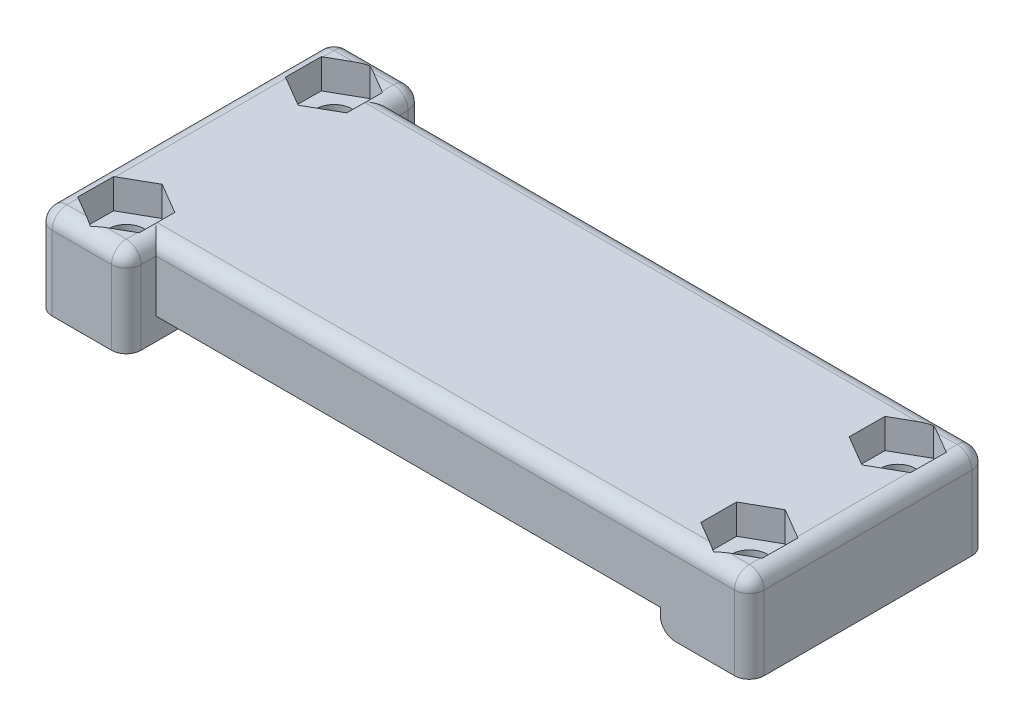
SolidWorks part; units mm, degrees
material "ABS PC"
ref_plane "前基準面" through (0, 0, 0) normal (0, 0, 1) x (1, 0, 0)
ref_plane "上基準面" through (0, 0, 0) normal (0, 1, 0) x (1, 0, 0)
ref_plane "右基準面" through (0, 0, 0) normal (1, 0, 0) x (0, 0, -1)
sketch "草圖1" plane through (0, 0, 0) normal (0, 1, 0) x (1, 0, 0)
  line L0 (0, 0) -> (-20, 0) construction
  line L1 (-20, -8) -> (20, -8)
  line L2 (-20, -4) -> (-20, 4)
  line L3 (-20, 8) -> (20, 8)
  line L4 (20, -8) -> (20, 8)
  line L5 (-20, 4) -> (-26, 4)
  line L6 (-26, 4) -> (-26, 10)
  line L7 (-26, 10) -> (-20, 10)
  line L8 (-20, 10) -> (-20, 8)
  line L9 (-20, -10) -> (-20, -8)
  line L10 (-26, -10) -> (-20, -10)
  line L11 (-26, -4) -> (-26, -10)
  line L12 (-20, -4) -> (-26, -4)
  dimension "D1" = 16
  dimension "D3" = 20
  dimension "D4" = 40
extrude "填料-伸長1" add sketch "草圖1" along normal blind 6
sketch "草圖2" plane through (0, 0, 0) normal (0, 1, 0) x (1, 0, 0)
  line L1 (-26, 4) -> (-20, 4)
  line L2 (-26, 4) -> (-26, -4)
  line L3 (-26, -4) -> (-20, -4)
  line L4 (-20, 4) -> (-20, -4)
extrude "填料-伸長2" add sketch "草圖2" along normal blind 6
sketch "草圖4" plane through (0, 0, 0) normal (0, 1, 0) x (1, 0, 0)
  line L0 (-20, 0) -> (0, 0) construction
  line L1 (-26, 10) -> (-23, 10) construction
  line L2 (-26, -10) -> (-23, -10) construction
  line L3 (-26, 10) -> (-20, 10) construction
  line L4 (-23, 10) -> (-23, 7) construction
  line L5 (-23, -10) -> (-23, -7) construction
  line L6 (-25.0866, -8.1859) -> (-23.0163, -9.4)
  line L7 (-20.9297, -8.2141) -> (-20.9134, -5.8141)
  line L8 (-23.0163, -9.4) -> (-20.9297, -8.2141)
  line L9 (-22.9837, -4.6) -> (-25.0703, -5.7859)
  line L10 (-22.9837, 9.4) -> (-25.0703, 8.2141)
  line L11 (-25.0703, 8.2141) -> (-25.0866, 5.8141)
  line L12 (-25.0866, 5.8141) -> (-23.0163, 4.6)
  line L13 (-23.0163, 4.6) -> (-20.9297, 5.7859)
  line L14 (-20.9297, 5.7859) -> (-20.9134, 8.1859)
  line L15 (-20.9134, 8.1859) -> (-22.9837, 9.4)
  line L16 (-25.0703, -5.7859) -> (-25.0866, -8.1859)
  line L17 (-20.9134, -5.8141) -> (-22.9837, -4.6)
  line L19 (19.0866, 6.1859) -> (17.0163, 7.4)
  line L20 (14.9297, 6.2141) -> (14.9134, 3.8141)
  line L21 (14.9134, 3.8141) -> (16.9837, 2.6)
  line L22 (16.9837, 2.6) -> (19.0703, 3.7859)
  line L23 (17.0163, 7.4) -> (14.9297, 6.2141)
  line L24 (19.0703, 3.7859) -> (19.0866, 6.1859)
  line L25 (19.0866, -3.8141) -> (17.0163, -2.6)
  line L26 (14.9297, -3.7859) -> (14.9134, -6.1859)
  line L27 (14.9134, -6.1859) -> (16.9837, -7.4)
  line L28 (16.9837, -7.4) -> (19.0703, -6.2141)
  line L29 (17.0163, -2.6) -> (14.9297, -3.7859)
  line L30 (19.0703, -6.2141) -> (19.0866, -3.8141)
  circle A0 centre (-23, -7) radius 2.0785 construction
  circle A1 centre (-23, 7) radius 2.0785 construction
  circle A2 centre (17, 5) radius 2.0785 construction
  circle A3 centre (17, -5) radius 2.0785 construction
  point P19 (-25.1955, 7)
  point P21 (-25.3, -7)
  point P27 (14.8045, 5)
  point P33 (14.8045, -5)
  dimension "D1" = 4.8
  dimension "D2" = 4.8
  dimension "D3" = 4.8
  dimension "D4" = 4.8
extrude "除料-伸長2" cut sketch "草圖4" along normal blind 2 from offset 4
fillet "圓角8" radius 1 2 edges at (0, 6, -8) (0, 6, 8)
fillet "圓角9" radius 1 5 edges at (20, 2.5, 8) (20, 5.7071, 7.7071) (20, 2.5, -8) (20, 5.7071, -7.7071) (20, 6, 0)
fillet "圓角10" radius 1 1 edges at (-20, 6, -8.5)
fillet "圓角11" radius 1 1 edges at (-20, 6, 8.5)
fillet "圓角12" radius 1 6 edges at (-23.5, 6, -10) (-20.2929, 5.7071, -10) (-23.5, 6, 10) (-20.2929, 5.7071, 10) (-20, 2.5, -10) (-20, 2.5, 10)
fillet "圓角13" radius 1 5 edges at (-26, 5.7071, 9.7071) (-26, 6, 0) (-26, 5.7071, -9.7071) (-26, 2.5, 10) (-26, 2.5, -10)
sketch "草圖6" plane through (0, 0, 0) normal (0, 1, 0) x (1, 0, 0)
  line L0 (-20, 8) -> (20, 8) construction
  line L1 (-20, -10) -> (-26, -10) construction
  line L2 (-20, -10) -> (-20, 10) construction
  line L3 (-20, 10) -> (-26, 10) construction
  line L4 (-26, -10) -> (-26, 10) construction
  line L5 (20, -8) -> (14, -8) construction
  line L6 (20, -8) -> (20, 8) construction
  line L7 (20, 8) -> (14, 8) construction
  line L8 (14, -8) -> (14, 8) construction
  dimension "D1" = 6
sketch "草圖8" plane through (0, 0, 0) normal (0, 1, 0) x (1, 0, 0)
  line L0 (-20, 4) -> (-20, 8)
  line L1 (-20, -8) -> (14, -8)
  line L2 (-20, -8) -> (-20, -4)
  line L3 (-20, 8) -> (14, 8)
  line L4 (14, -8) -> (14, 8)
  line L5 (-20, -4) -> (-26, -4)
  line L7 (-20, 4) -> (-26, 4)
  line L8 (-26, -4) -> (-26, 4)
extrude "除料-伸長5" cut sketch "草圖8" along normal blind 1.5
fillet "圓角14" radius 1 1 edges at (14, 0, 0)
sketch "草圖9" plane through (0, 0, 0) normal (0, 1, 0) x (1, 0, 0)
  line L0 (-22.9837, 9.4) -> (-23.0163, 4.6) construction
  line L1 (-22.9837, -4.6) -> (-23.0163, -9.4) construction
  line L2 (-25.0703, 8.2141) -> (-25.0866, 5.8141) construction
  line L3 (-25.0785, 7.0141) -> (-23, 7) construction
  line L4 (-25.0785, -6.9859) -> (-23, -7) construction
  line L5 (17.0163, 7.4) -> (16.9837, 2.6) construction
  line L6 (14.9215, 5.0141) -> (17, 5) construction
  line L7 (17.0163, -2.6) -> (16.9837, -7.4) construction
  line L8 (14.9215, -4.9859) -> (17, -5) construction
  circle A0 centre (-23, 7) radius 1.2
  circle A1 centre (-23, -7) radius 1.2
  circle A2 centre (17, 5) radius 1.2
  circle A3 centre (17, -5) radius 1.2
extrude "除料-伸長6" cut sketch "草圖9" along normal blind 5
